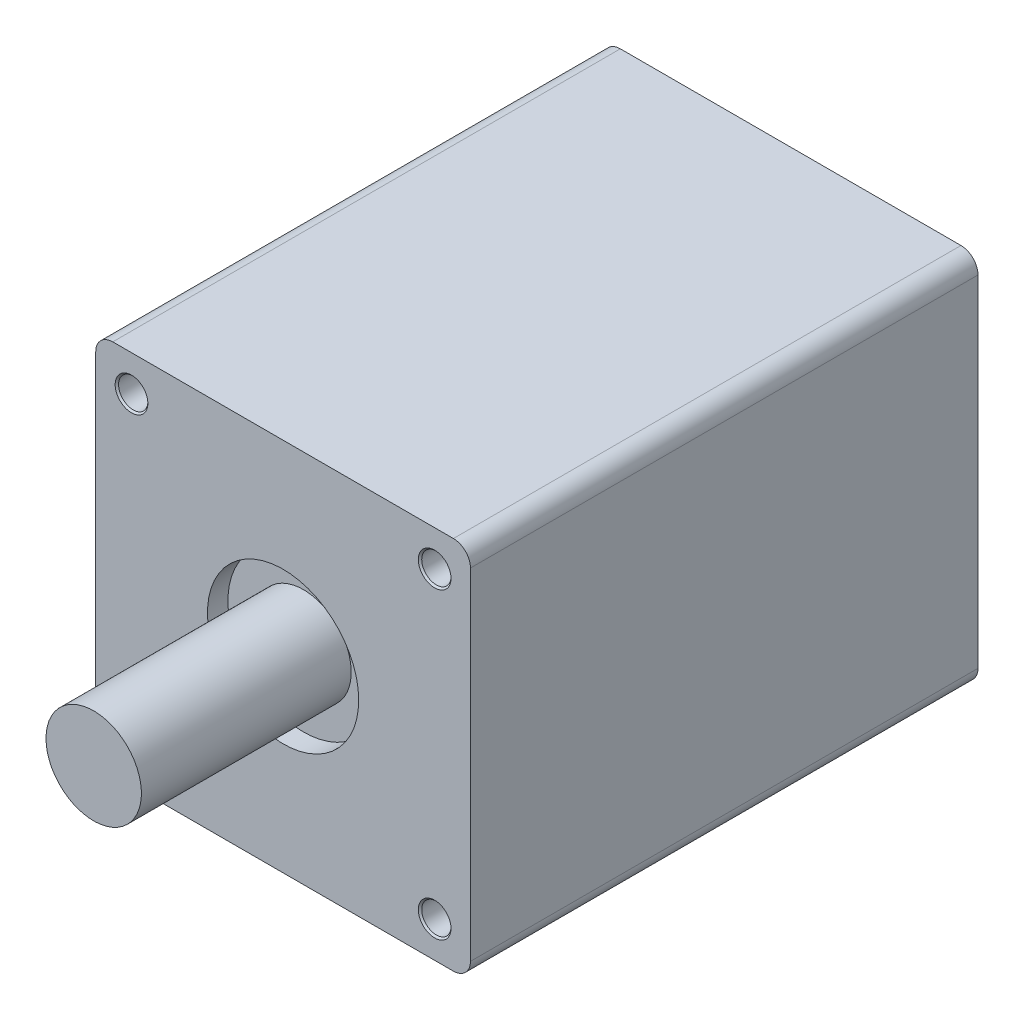
SolidWorks part; units mm, degrees
ref_plane "Front Plane" through (0, 0, 0) normal (0, 0, 1) x (1, 0, 0)
ref_plane "Top Plane" through (0, 0, 0) normal (0, 1, 0) x (1, 0, 0)
ref_plane "Right Plane" through (0, 0, 0) normal (1, 0, 0) x (0, 0, -1)
sketch "Sketch1" plane through (0, 0, 0) normal (0, 0, 1) x (1, 0, 0)
  line L1 (50, -55) -> (-50, -55)
  line L2 (55, -50) -> (55, 50)
  line L3 (50, 55) -> (-50, 55)
  line L4 (-55, -50) -> (-55, 50)
  line L5 (55, -55) -> (-55, 55) construction
  line L6 (55, 55) -> (-55, -55) construction
  arc A0 (50, -55) -> (55, -50) centre (50, -50) ccw
  arc A1 (-50, -55) -> (-55, -50) centre (-50, -50) cw
  arc A2 (55, 50) -> (50, 55) centre (50, 50) ccw
  arc A3 (-50, 55) -> (-55, 50) centre (-50, 50) ccw
  circle A4 centre (-44.5, 44.5) radius 4.3
  circle A5 centre (44.5, 44.5) radius 4.3
  circle A6 centre (-44.5, -44.5) radius 4.3
  circle A7 centre (44.5, -44.5) radius 4.3
  point P0 (0, 0)
  dimension "D3" = 5
  dimension "D4" = 8.6
  dimension "D5" = 89
  dimension "D6" = 89
  dimension "D1" = 110
  dimension "D2" = 110
  dimension "D7" = 44.5
  dimension "D8" = 44.5
extrude "Boss-Extrude1" add sketch "Sketch1" along normal blind 22
sketch "Sketch2" plane through (0, 0, 0) normal (0, 0, -1) x (-1, 0, 0)
  line L0 (-51, 36.6) -> (-43.6, 36.6)
  line L1 (-36.6, 43.6) -> (-36.6, 51)
  line L2 (-32.6, 55) -> (-50, 55)
  line L3 (-55, 50) -> (-55, 32.6)
  line L4 (-50, -55) -> (50, -55)
  line L5 (55, -50) -> (55, 50)
  line L6 (50, 55) -> (-50, 55)
  line L7 (-55, 50) -> (-55, -50)
  line L8 (0, 55) -> (0, -55) construction
  line L9 (-50, 55) -> (50, 55) construction
  line L10 (50, -55) -> (-50, -55) construction
  line L11 (0, 0) -> (-55, 0) construction
  line L12 (-55, -50) -> (-55, 50) construction
  line L13 (55, 50) -> (55, 32.6)
  line L14 (32.6, 55) -> (50, 55)
  line L15 (36.6, 43.6) -> (36.6, 51)
  line L16 (51, 36.6) -> (43.6, 36.6)
  line L17 (51, -36.6) -> (43.6, -36.6)
  line L18 (36.6, -43.6) -> (36.6, -51)
  line L19 (32.6, -55) -> (50, -55)
  line L20 (55, -50) -> (55, -32.6)
  line L21 (-55, -50) -> (-55, -32.6)
  line L22 (-32.6, -55) -> (-50, -55)
  line L23 (-36.6, -43.6) -> (-36.6, -51)
  line L24 (-51, -36.6) -> (-43.6, -36.6)
  arc A0 (-43.6, 36.6) -> (-36.6, 43.6) centre (-43.6, 43.6) ccw
  arc A1 (-51, 36.6) -> (-55, 32.6) centre (-51, 32.6) ccw
  arc A2 (-36.6, 51) -> (-32.6, 55) centre (-32.6, 51) cw
  arc A3 (50, 55) -> (55, 50) centre (50, 50) cw
  arc A4 (-55, -50) -> (-50, -55) centre (-50, -50) ccw
  arc A5 (50, -55) -> (55, -50) centre (50, -50) ccw
  arc A6 (55, 50) -> (50, 55) centre (50, 50) ccw
  arc A7 (-50, 55) -> (-55, 50) centre (-50, 50) ccw
  arc A8 (36.6, 51) -> (32.6, 55) centre (32.6, 51) ccw
  arc A9 (51, 36.6) -> (55, 32.6) centre (51, 32.6) cw
  arc A10 (43.6, 36.6) -> (36.6, 43.6) centre (43.6, 43.6) cw
  arc A11 (-50, 55) -> (-55, 50) centre (-50, 50) ccw
  arc A12 (43.6, -36.6) -> (36.6, -43.6) centre (43.6, -43.6) ccw
  arc A13 (51, -36.6) -> (55, -32.6) centre (51, -32.6) ccw
  arc A14 (36.6, -51) -> (32.6, -55) centre (32.6, -51) cw
  arc A15 (50, -55) -> (55, -50) centre (50, -50) ccw
  arc A16 (-50, -55) -> (-55, -50) centre (-50, -50) cw
  arc A17 (-36.6, -51) -> (-32.6, -55) centre (-32.6, -51) ccw
  arc A18 (-51, -36.6) -> (-55, -32.6) centre (-51, -32.6) cw
  arc A19 (-43.6, -36.6) -> (-36.6, -43.6) centre (-43.6, -43.6) cw
  point P17 (-36.6, 36.6)
  point P20 (-55, 36.6)
  point P43 (55, 36.6)
  point P44 (36.6, 36.6)
  point P54 (36.6, -36.6)
  point P55 (55, -36.6)
  point P65 (-55, -36.6)
  point P66 (-36.6, -36.6)
  dimension "D4" = 7
  dimension "D5" = 4
  dimension "D3" = 18.4
  dimension "D1" = 0
extrude "Cut-Extrude1" cut sketch "Sketch2" against normal blind 10
chamfer "Chamfer1" distance 0.5 angle 45 8 edges at (-48.8, -44.5, 10) (-40.2, -44.5, 22) (48.8, -44.5, 22) (48.8, -44.5, 10) (40.2, 44.5, 10) (48.8, 44.5, 22) (-40.2, 44.5, 22) (-40.2, 44.5, 10)
sketch "Sketch3" plane through (0, 0, 22) normal (0, 0, 1) x (1, 0, 0)
  line L0 (50, 55) -> (-50, 55) construction
  line L1 (-39, 50) -> (-39, 60.5998)
  line L2 (-39, 60.5998) -> (-25, 60.5998)
  line L3 (-25, 60.5998) -> (-25, 50)
  line L4 (-55, 50) -> (-55, -50) construction
  arc A0 (-39, 50) -> (-25, 50) centre (-32, 50) ccw
  dimension "D2" = 14
  dimension "D1" = 5
  dimension "D3" = 16
extrude "Cut-Extrude2" cut sketch "Sketch3" against normal blind 5.6
fillet "Fillet1" radius 1.5 2 edges at (-39, 55, 19.2) (-25, 55, 19.2)
sketch "Sketch6" plane through (0, 0, 22) normal (0, 0, 1) x (1, 0, 0)
  circle A0 centre (0, 0) radius 27.775
  dimension "D1" = 55.55
extrude "Boss-Extrude2" add sketch "Sketch6" along normal blind 1.9
sketch "Sketch7" plane through (0, 0, 0) normal (1, 0, 0) x (0, 0, -1)
  line L0 (0, 0) -> (-55.0013, 0) construction
  line L1 (-22, 27.775) -> (-21.7, 27.775)
  line L2 (-22, -50) -> (-22, 50) construction
  line L3 (-22, 27.775) -> (-22, -27.775) construction
  line L4 (-21.7, 27.775) -> (-21.7, 29.9)
  line L5 (-21.7, 29.9) -> (-22, 31.1)
  line L6 (-22, 31.1) -> (-22, 27.775)
  line L7 (-23.9, 27.775) -> (-23.9, -27.775) construction
  line L8 (-23.9, 23.3) -> (-16, 23.3)
  line L9 (-16, 23.3) -> (-16, 10)
  line L10 (-16, 10) -> (-23.9, 10)
  line L11 (-23.9, 10) -> (-23.9, 23.3)
  dimension "D1" = 55.55
  dimension "D2" = 2.2
  dimension "D3" = 59.8
  dimension "D4" = 62.2
  dimension "D5" = 46.6
  dimension "D6" = 20
  dimension "D7" = 7.9
revolve "Cut-Revolve1" cut sketch "Sketch7" angle 360 about L0
sketch "Sketch8" plane through (0, 0, 16) normal (0, 0, 1) x (1, 0, 0)
  circle A0 centre (0, 0) radius 14
  circle A1 centre (0, 0) radius 22.2
  dimension "D1" = 28
  dimension "D2" = 44.4
split line "Split Line1"
sketch "Sketch9" plane through (0, 0, 23.9) normal (0, 0, 1) x (1, 0, 0)
  circle A0 centre (0, 0) radius 9.5
  dimension "D1" = 19
extrude "Boss-Extrude3" add sketch "Sketch9" along normal blind 53.7
chamfer "Chamfer2" distance 1 angle 45 1 edges at (9.5, 0, 77.6)
sketch "Sketch11" plane through (0, 0, 77.6) normal (0, 0, 1) x (1, 0, 0)
  line L1 (3, 13.1) -> (-3, 13.1)
  line L2 (3, 13.1) -> (3, 5.9)
  line L3 (3, 5.9) -> (-3, 5.9)
  line L4 (-3, 13.1) -> (-3, 5.9)
  line L5 (3, 13.1) -> (-3, 5.9) construction
  line L6 (3, 5.9) -> (-3, 13.1) construction
  circle A0 centre (0, 0) radius 9.5 construction
  circle A1 centre (0, 0) radius 9.5 construction
  point P0 (0, 9.5)
  dimension "D1" = 6
  dimension "D2" = 3.6
extrude "Cut-Extrude3" cut sketch "Sketch11" against normal blind 35
fillet "Fillet2" radius 2.95 2 edges at (-3, 7.4569, 42.6) (3, 7.4569, 42.6)
sketch "Sketch12" plane through (0, 5.9, 0) normal (0, 1, 0) x (1, 0, 0)
  line L0 (-0.05, -45.55) -> (-0.05, -74.55) construction
  line L1 (2.95, -45.55) -> (2.95, -74.55)
  line L2 (-3.05, -45.55) -> (-3.05, -74.55)
  arc A0 (2.95, -45.55) -> (-3.05, -45.55) centre (-0.05, -45.55) ccw
  arc A1 (-3.05, -74.55) -> (2.95, -74.55) centre (-0.05, -74.55) ccw
  point P3 (-0.05, -60.05)
  dimension "D2" = 3
  dimension "D1" = 29
extrude "Boss-Extrude4" add sketch "Sketch12" along normal blind 6 separate body
sketch "Sketch13" plane through (0, 0, 77.6) normal (0, 0, 1) x (1, 0, 0)
  circle A0 centre (0, 0) radius 1.2695
extrude "Cut-Extrude4" cut sketch "Sketch13" against normal blind 5
chamfer "Chamfer3" distance 0.5 angle 74 1 edges at (1.2695, 0, 77.6) first distance on face at (1.2695, 0, 77.6)
pattern_circular "CirPattern2" count 4 over 360 about axis through (0, 0, 0) along (0, 0, 1) of "Cut-Extrude2"
fillet "Fillet3" radius 1.5 6 edges at (-55, -39, 19.2) (-55, -25, 19.2) (39, -55, 19.2) (25, -55, 19.2) (55, 25, 19.2) (55, 39, 19.2)
sketch "Sketch14" plane through (0, 0, 16.4) normal (0, 0, 1) x (1, 0, 0)
  circle A0 centre (-32, 50) radius 4.5
  dimension "D1" = 9
extrude "Boss-Extrude5" add sketch "Sketch14" along normal blind 3 separate body
fillet "Fillet4" radius 0.5 2 edges at (-27.5, 50, 16.4) (-27.5, 50, 19.4)
sketch "Sketch15" plane through (0, 0, 19.4) normal (0, 0, 1) x (1, 0, 0)
  line L0 (-31.2058, 50.8067) -> (-28.6738, 50.8067)
  line L1 (-32.7942, 46.7257) -> (-31.2058, 46.7257)
  line L2 (-32.7942, 46.7257) -> (-32.7942, 49.1933)
  line L3 (-32.7942, 53.2743) -> (-31.2058, 53.2743)
  line L4 (-31.2058, 46.7257) -> (-31.2058, 49.1933)
  line L7 (-35.3262, 49.1933) -> (-32.7942, 49.1933)
  line L8 (-35.3262, 49.1933) -> (-35.3262, 50.8067)
  line L9 (-35.3262, 50.8067) -> (-32.7942, 50.8067)
  line L10 (-28.6738, 49.1933) -> (-28.6738, 50.8067)
  line L15 (-31.2058, 49.1933) -> (-28.6738, 49.1933)
  line L18 (-32.7942, 50.8067) -> (-32.7942, 53.2743)
  line L19 (-31.2058, 50.8067) -> (-31.2058, 53.2743)
  point P0 (-32, 50)
  point P6 (-32, 50)
extrude "Cut-Extrude5" cut sketch "Sketch15" against normal blind 1.5
chamfer "Chamfer4" distance 1 angle 68 4 edges at (-32, 46.7257, 17.9) (-32, 53.2743, 17.9) (-35.3262, 50, 17.9) (-28.6738, 50, 17.9) first distance on face at (-32, 46.7257, 18.65) first distance on face at (-32, 53.2743, 18.65) first distance on face at (-35.3262, 50, 18.65) first distance on face at (-28.6738, 50, 18.65)
pattern_circular "CirPattern3" count 4 over 360 about axis through (0, 0, 0) along (0, 0, 1) of bodies 113
sketch "Sketch16" plane through (0, 0, 0) normal (0, 0, -1) x (-1, 0, 0)
  line L12 (55, -32.6) -> (55, 32.6)
  line L13 (51, 36.6) -> (43.6, 36.6)
  line L14 (36.6, 43.6) -> (36.6, 51)
  line L15 (32.6, 55) -> (-32.6, 55)
  line L16 (-36.6, 51) -> (-36.6, 43.6)
  line L17 (-43.6, 36.6) -> (-51, 36.6)
  line L18 (-55, 32.6) -> (-55, -32.6)
  line L19 (-51, -36.6) -> (-43.6, -36.6)
  line L20 (-36.6, -43.6) -> (-36.6, -51)
  line L21 (-32.6, -55) -> (32.6, -55)
  line L22 (36.6, -51) -> (36.6, -43.6)
  line L23 (43.6, -36.6) -> (51, -36.6)
  line L24 (55, -32.6) -> (55, 32.6)
  line L25 (51, 36.6) -> (43.6, 36.6)
  line L26 (36.6, 43.6) -> (36.6, 51)
  line L27 (32.6, 55) -> (-32.6, 55)
  line L28 (-36.6, 51) -> (-36.6, 43.6)
  line L29 (-43.6, 36.6) -> (-51, 36.6)
  line L30 (-55, 32.6) -> (-55, -32.6)
  line L31 (-51, -36.6) -> (-43.6, -36.6)
  line L32 (-36.6, -43.6) -> (-36.6, -51)
  line L33 (-32.6, -55) -> (32.6, -55)
  line L34 (36.6, -51) -> (36.6, -43.6)
  line L35 (43.6, -36.6) -> (51, -36.6)
  arc A12 (55, 32.6) -> (51, 36.6) centre (51, 32.6) ccw
  arc A13 (36.6, 43.6) -> (43.6, 36.6) centre (43.6, 43.6) ccw
  arc A14 (36.6, 51) -> (32.6, 55) centre (32.6, 51) ccw
  arc A15 (-32.6, 55) -> (-36.6, 51) centre (-32.6, 51) ccw
  arc A16 (-43.6, 36.6) -> (-36.6, 43.6) centre (-43.6, 43.6) ccw
  arc A17 (-51, 36.6) -> (-55, 32.6) centre (-51, 32.6) ccw
  arc A18 (-55, -32.6) -> (-51, -36.6) centre (-51, -32.6) ccw
  arc A19 (-36.6, -43.6) -> (-43.6, -36.6) centre (-43.6, -43.6) ccw
  arc A20 (-36.6, -51) -> (-32.6, -55) centre (-32.6, -51) ccw
  arc A21 (32.6, -55) -> (36.6, -51) centre (32.6, -51) ccw
  arc A22 (43.6, -36.6) -> (36.6, -43.6) centre (43.6, -43.6) ccw
  arc A23 (51, -36.6) -> (55, -32.6) centre (51, -32.6) ccw
  arc A24 (55, 32.6) -> (51, 36.6) centre (51, 32.6) ccw
  arc A25 (36.6, 43.6) -> (43.6, 36.6) centre (43.6, 43.6) ccw
  arc A26 (36.6, 51) -> (32.6, 55) centre (32.6, 51) ccw
  arc A27 (-32.6, 55) -> (-36.6, 51) centre (-32.6, 51) ccw
  arc A28 (-43.6, 36.6) -> (-36.6, 43.6) centre (-43.6, 43.6) ccw
  arc A29 (-51, 36.6) -> (-55, 32.6) centre (-51, 32.6) ccw
  arc A30 (-55, -32.6) -> (-51, -36.6) centre (-51, -32.6) ccw
  arc A31 (-36.6, -43.6) -> (-43.6, -36.6) centre (-43.6, -43.6) ccw
  arc A32 (-36.6, -51) -> (-32.6, -55) centre (-32.6, -51) ccw
  arc A33 (32.6, -55) -> (36.6, -51) centre (32.6, -51) ccw
  arc A34 (43.6, -36.6) -> (36.6, -43.6) centre (43.6, -43.6) ccw
  arc A35 (51, -36.6) -> (55, -32.6) centre (51, -32.6) ccw
  dimension "D1" = 0
extrude "Boss-Extrude6" add sketch "Sketch16" along normal blind 107 separate body
sketch "Sketch17" plane through (0, 0, -107) normal (0, 0, -1) x (-1, 0, 0)
  line L12 (55, -32.6) -> (55, 32.6)
  line L13 (51, 36.6) -> (43.6, 36.6)
  line L14 (36.6, 43.6) -> (36.6, 51)
  line L15 (32.6, 55) -> (-32.6, 55)
  line L16 (-36.6, 51) -> (-36.6, 43.6)
  line L17 (-43.6, 36.6) -> (-51, 36.6)
  line L18 (-55, 32.6) -> (-55, -32.6)
  line L19 (-51, -36.6) -> (-43.6, -36.6)
  line L20 (-36.6, -43.6) -> (-36.6, -51)
  line L21 (-32.6, -55) -> (32.6, -55)
  line L22 (36.6, -51) -> (36.6, -43.6)
  line L23 (43.6, -36.6) -> (51, -36.6)
  line L24 (55, -32.6) -> (55, 32.6)
  line L25 (51, 36.6) -> (43.6, 36.6)
  line L26 (36.6, 43.6) -> (36.6, 51)
  line L27 (32.6, 55) -> (-32.6, 55)
  line L28 (-36.6, 51) -> (-36.6, 43.6)
  line L29 (-43.6, 36.6) -> (-51, 36.6)
  line L30 (-55, 32.6) -> (-55, -32.6)
  line L31 (-51, -36.6) -> (-43.6, -36.6)
  line L32 (-36.6, -43.6) -> (-36.6, -51)
  line L33 (-32.6, -55) -> (32.6, -55)
  line L34 (36.6, -51) -> (36.6, -43.6)
  line L35 (43.6, -36.6) -> (51, -36.6)
  arc A12 (51, -36.6) -> (55, -32.6) centre (51, -32.6) ccw
  arc A13 (55, 32.6) -> (51, 36.6) centre (51, 32.6) ccw
  arc A14 (36.6, 43.6) -> (43.6, 36.6) centre (43.6, 43.6) ccw
  arc A15 (36.6, 51) -> (32.6, 55) centre (32.6, 51) ccw
  arc A16 (-32.6, 55) -> (-36.6, 51) centre (-32.6, 51) ccw
  arc A17 (-43.6, 36.6) -> (-36.6, 43.6) centre (-43.6, 43.6) ccw
  arc A18 (-51, 36.6) -> (-55, 32.6) centre (-51, 32.6) ccw
  arc A19 (-55, -32.6) -> (-51, -36.6) centre (-51, -32.6) ccw
  arc A20 (-36.6, -43.6) -> (-43.6, -36.6) centre (-43.6, -43.6) ccw
  arc A21 (-36.6, -51) -> (-32.6, -55) centre (-32.6, -51) ccw
  arc A22 (32.6, -55) -> (36.6, -51) centre (32.6, -51) ccw
  arc A23 (43.6, -36.6) -> (36.6, -43.6) centre (43.6, -43.6) ccw
  arc A24 (51, -36.6) -> (55, -32.6) centre (51, -32.6) ccw
  arc A25 (55, 32.6) -> (51, 36.6) centre (51, 32.6) ccw
  arc A26 (36.6, 43.6) -> (43.6, 36.6) centre (43.6, 43.6) ccw
  arc A27 (36.6, 51) -> (32.6, 55) centre (32.6, 51) ccw
  arc A28 (-32.6, 55) -> (-36.6, 51) centre (-32.6, 51) ccw
  arc A29 (-43.6, 36.6) -> (-36.6, 43.6) centre (-43.6, 43.6) ccw
  arc A30 (-51, 36.6) -> (-55, 32.6) centre (-51, 32.6) ccw
  arc A31 (-55, -32.6) -> (-51, -36.6) centre (-51, -32.6) ccw
  arc A32 (-36.6, -43.6) -> (-43.6, -36.6) centre (-43.6, -43.6) ccw
  arc A33 (-36.6, -51) -> (-32.6, -55) centre (-32.6, -51) ccw
  arc A34 (32.6, -55) -> (36.6, -51) centre (32.6, -51) ccw
  arc A35 (43.6, -36.6) -> (36.6, -43.6) centre (43.6, -43.6) ccw
  dimension "D1" = 0
extrude "Boss-Extrude7" add sketch "Sketch17" along normal blind 20 separate body
sketch "Sketch18" plane through (0, 0, -127) normal (0, 0, -1) x (-1, 0, 0)
  circle A0 centre (0, 0) radius 17.5
  dimension "D1" = 35
extrude "Cut-Extrude6" cut sketch "Sketch18" against normal blind 4.6
sketch "Sketch19" plane through (0, 55, 0) normal (0, 1, 0) x (1, 0, 0)
  line L0 (0, 127) -> (0, 112.5319) construction
  line L1 (-32.6, 127) -> (32.6, 127) construction
  line L2 (-7, 119.5319) -> (-7, 106.5319)
  line L3 (-7, 106.5319) -> (7, 106.5319)
  line L4 (7, 106.5319) -> (7, 119.5319)
  line L5 (0, 106.5319) -> (0, 90.3404) construction
  arc A0 (7, 119.5319) -> (-7, 119.5319) centre (0, 119.5319) ccw
  dimension "D1" = 14
  dimension "D2" = 13
extrude "Boss-Extrude8" add sketch "Sketch19" along normal blind 2 separate body
sketch "Sketch20" plane through (0, 57, 0) normal (0, 1, 0) x (1, 0, 0)
  circle A0 centre (-1.528, 111.9593) radius 0.7818
  circle A1 centre (0, 111.1776) radius 0.7818
  circle A2 centre (1.0664, 112.3932) radius 0.7557
  circle A3 centre (0.9858, 109.9174) radius 0.7776
extrude "Boss-Extrude9" add sketch "Sketch20" along normal blind 5
sketch "Sketch22" plane through (0, 0, 22) normal (0, 0, 1) x (1, 0, 0)
  line L0 (-40.5, 55) -> (-50, 55) construction
  line L1 (-15.0604, 38.9945) -> (-31.5168, 38.9945)
  line L2 (-15.0604, 38.9945) -> (-15.0604, 55)
  line L3 (-15.0604, 55) -> (-45.25, 55)
  line L4 (-45.25, 52.7278) -> (-45.25, 55)
  line L10 (36.5258, -39.3657) -> (15.8682, -39.3657)
  line L11 (36.5258, -39.3657) -> (42.9885, -55)
  line L12 (42.9885, -55) -> (15.8682, -55)
  line L13 (15.8682, -39.3657) -> (15.8682, -55)
  line L15 (-55, -20.2084) -> (-35.6026, -20.2084)
  line L16 (-55, -20.2084) -> (-55, -43.0587)
  line L17 (-55, -43.0587) -> (-35.6026, -34.6341)
  line L18 (-35.6026, -20.2084) -> (-35.6026, -34.6341)
  line L20 (-45.25, 52.7278) -> (-31.5168, 38.9945)
  line L22 (-55, 50) -> (-55, -23.5) construction
  line L23 (40.5, -55) -> (50, -55) construction
  line L24 (36.5258, 33.1088) -> (55, 45.25)
  line L25 (55, 40.5) -> (55, 50) construction
  line L26 (55, 45.25) -> (55, 16.8367)
  line L27 (55, -50) -> (55, 23.5) construction
  line L28 (55, 16.8367) -> (36.5258, 33.1088)
extrude "Boss-Extrude10" add sketch "Sketch22" against normal up to vertex (22 mm away) up to point (-43.6, -36.6, 0)
sketch "Sketch23" plane through (0, 0, 10) normal (0, 0, -1) x (-1, 0, 0)
  line L1 (-50, 55) -> (50, 55)
  line L2 (-55, 50) -> (-55, -50)
  line L3 (-50, -55) -> (50, -55)
  line L4 (55, 50) -> (55, -50)
  line L6 (55, 32.6) -> (55, 50) construction
  line L7 (-32.6, 55) -> (-50, 55) construction
  line L8 (-55, 50) -> (-55, 45.25) construction
  line L9 (32.6, -55) -> (50, -55) construction
  arc A0 (-55, -50) -> (-50, -55) centre (-50, -50) ccw
  arc A1 (50, -55) -> (55, -50) centre (50, -50) ccw
  arc A2 (50, 55) -> (55, 50) centre (50, 50) cw
  arc A3 (-50, 55) -> (-55, 50) centre (-50, 50) ccw
  dimension "D1" = 5
extrude "Boss-Extrude11" add sketch "Sketch23" along normal up to vertex (137 mm away) up to point (55, 32.6, -127)
sketch "Sketch25" plane through (0, 55, 0) normal (0, 1, 0) x (1, 0, 0)
  line L1 (-17.4711, 65.0334) -> (20.2665, 65.0334)
  line L2 (-17.4711, 65.0334) -> (-17.4711, 131.1242)
  line L3 (-17.4711, 131.1242) -> (20.2665, 131.1242)
  line L4 (20.2665, 65.0334) -> (20.2665, 131.1242)
extrude "Cut-Extrude9" cut sketch "Sketch25" along normal blind 53
sketch "Sketch26" plane through (0, 0, 23.9) normal (0, 0, 1) x (1, 0, 0)
  circle A0 centre (0, 0) radius 23.3
  circle A1 centre (0, 0) radius 39.0257
extrude "Boss-Extrude12" add sketch "Sketch26" against normal up to vertex (1.9 mm away) up to point (-55, 50, 22)
sketch "Sketch27" plane through (0, 0, 16) normal (0, 0, 1) x (1, 0, 0)
  circle A0 centre (0, 0) radius 14
extrude "Boss-Extrude13" add sketch "Sketch27" along normal up to vertex (61.6 mm away) up to point (-3, 7.953, 77.6)
sketch "Sketch28" plane through (0, 0, 23.9) normal (0, 0, 1) x (1, 0, 0)
  circle A0 centre (0, 0) radius 23.3
  circle A1 centre (0, 0) radius 22.2
extrude "Boss-Extrude14" add sketch "Sketch28" along a picked direction on the side against the normal up to next (7.9 mm away)
sketch "Sketch29" plane through (0, 0, 23.9) normal (0, 0, 1) x (1, 0, 0)
  circle A0 centre (0, 0) radius 39.0257
  circle A1 centre (0, 0) radius 22.2
extrude "Cut-Extrude10" cut sketch "Sketch29" against normal up to vertex (1.9 mm away) up to point (-55, 50, 22)
sketch "Sketch30" plane through (0, 0, 22) normal (0, 0, 1) x (1, 0, 0)
  circle A0 centre (0, 0) radius 31.1
  circle A1 centre (0, 0) radius 22.2
extrude "Boss-Extrude15" add sketch "Sketch30" against normal blind 30
